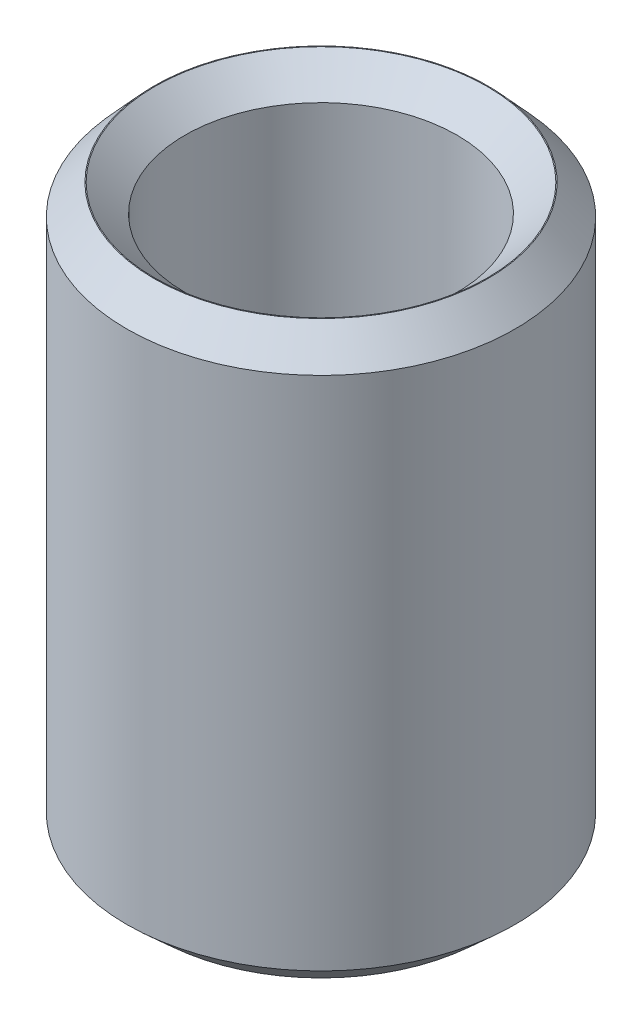
SolidWorks part; units mm, degrees
ref_plane "Front Plane" through (0, 0, 0) normal (0, 0, 1) x (1, 0, 0)
ref_plane "Top Plane" through (0, 0, 0) normal (0, 1, 0) x (1, 0, 0)
ref_plane "Right Plane" through (0, 0, 0) normal (1, 0, 0) x (0, 0, -1)
sketch "Sketch1" plane through (0, 0, 0) normal (0, 1, 0) x (1, 0, 0)
  circle A0 centre (0, 0) radius 22.5
  dimension "SLEEVE_OD" = 45
extrude "Boss-Extrude1" add sketch "Sketch1" along normal blind 66.376
sketch "Sketch2" plane through (0, 0, 0) normal (0, 1, 0) x (1, 0, 0)
  circle A0 centre (0, 0) radius 15.7673
  dimension "BORE_D" = 31.5347
extrude "Cut-Extrude1" cut sketch "Sketch2" along normal through all
chamfer "Chamfer1" distance 3.4714 angle 42.308 4 edges at (0, 66.376, 15.7673) (0, 0, 15.7673) (0, 0, 22.5) (0, 66.376, 22.5) first distance on face at (0, 66.376, 15.7673) first distance on face at (0, 0, 15.7673) first distance on face at (0, 66.376, 22.5)
